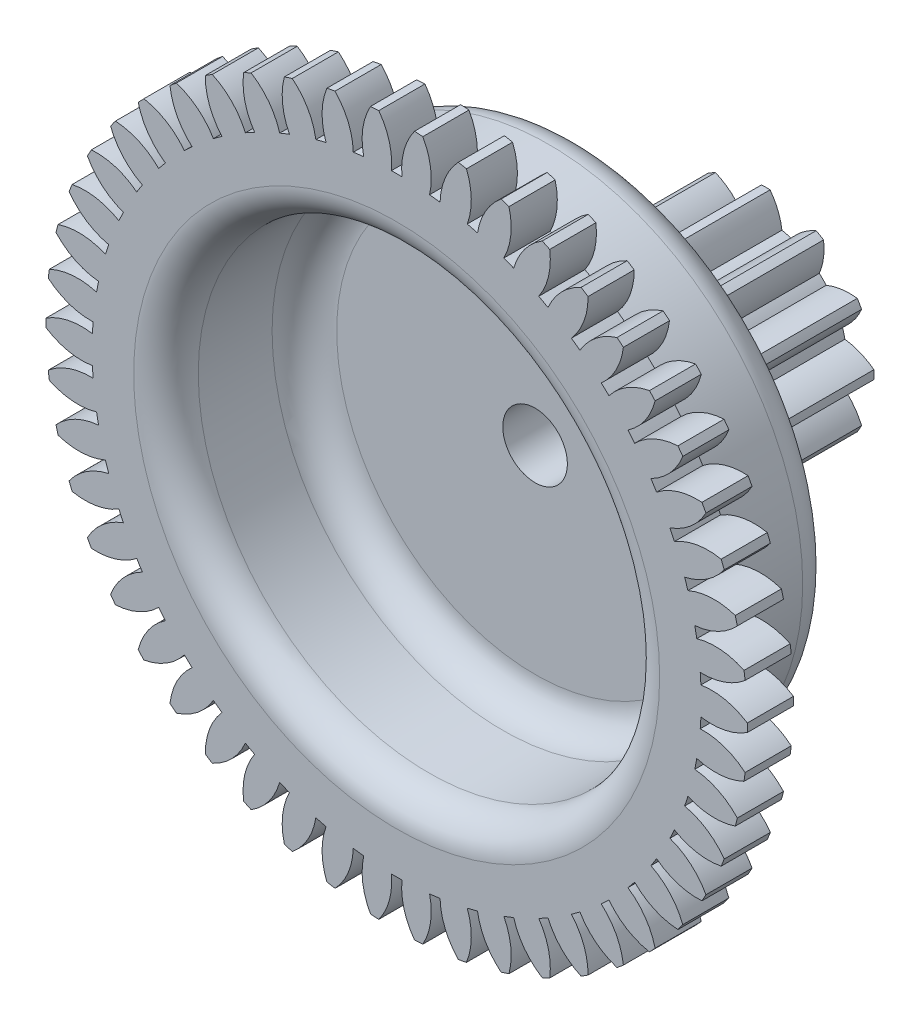
SolidWorks part; units mm, degrees
material "ABS PC"
ref_plane "Front Plane" through (0, 0, 0) normal (0, 0, 1) x (1, 0, 0)
ref_plane "Top Plane" through (0, 0, 0) normal (0, 1, 0) x (1, 0, 0)
ref_plane "Right Plane" through (0, 0, 0) normal (1, 0, 0) x (0, 0, -1)
sketch "Sketch1" plane through (0, 0, 0) normal (0, 0, 1) x (1, 0, 0)
  circle A0 centre (0, 0) radius 6.6
  dimension "D1" = 13.2
extrude "Extrude1" add sketch "Sketch1" along normal mid plane 1
sketch "Sketch2" plane through (0, 0, 0.5) normal (0, 0, 1) x (1, 0, 0)
  line L0 (-7.6, 0) -> (-6.6, 0) construction
  arc A2 (-6.5932, 0.3) -> (-6.5932, -0.3) centre (0, 0) ccw
  arc A3 (-7.5995, -0.09) -> (-6.5932, -0.3) centre (-6.8237, 1.1113) ccw
  arc A4 (-7.5995, 0.09) -> (-7.5995, -0.09) centre (0, 0) ccw
  arc A5 (-6.5932, 0.3) -> (-7.5995, 0.09) centre (-6.8235, -1.1124) ccw
  circle A12 centre (0, 0) radius 6.6 construction
  point P7 (0, 0)
  dimension "D1" = 1
  dimension "D2" = 1.4311
  dimension "D3" = 1.43
  dimension "D4" = 0.18
  dimension "D5" = 0.6
extrude "Extrude2" add sketch "Sketch2" against normal blind 1
pattern_circular "CirPattern1" count 50 over 360 about axis through (0, 0, 0.5) along (0, 0, -1) of "Extrude2"
sketch "Sketch3" plane through (0, 0, -0.5) normal (0, 0, -1) x (-1, 0, 0)
  circle A1 centre (0, 0) radius 5.5
  dimension "D2" = 11
extrude "Extrude4" add sketch "Sketch3" along normal blind 3
sketch "Sketch4" plane through (0, 0, -3.5) normal (0, 0, -1) x (-1, 0, 0)
  line L0 (0, 2.3452) -> (0, 0) construction
  arc A0 (-0.35, 1.7146) -> (0.35, 1.7146) centre (0, 0) ccw
  arc A1 (0.0929, 2.3433) -> (-0.0929, 2.3433) centre (0, 0) ccw
  arc A2 (-0.0929, 2.3433) -> (-0.35, 1.7146) centre (0.9732, 1.5404) ccw
  arc A6 (0.35, 1.7146) -> (0.0929, 2.3433) centre (-0.9732, 1.5404) ccw
  dimension "D1" = 3.5
  dimension "D2" = 1.3346
  dimension "D3" = 0.1857
  dimension "D4" = 0.7
  dimension "D5" = 2.3452
extrude "Extrude3" add sketch "Sketch4" along normal blind 4
pattern_circular "CirPattern2" count 12 over 360 about axis through (0, 0, -7.5) along (0, 0, 1) of "Extrude3"
sketch "Sketch5" plane through (0, 0, -7.5) normal (0, 0, -1) x (-1, 0, 0)
  circle A0 centre (0, 0) radius 0.7
  dimension "D1" = 1.4
extrude "Cut-Extrude2" cut sketch "Sketch5" against normal up to surface (8 mm away) up to face at (0, 0, 0.5)
sketch "Sketch6" plane through (0, 0, 0.5) normal (0, 0, 1) x (1, 0, 0)
  circle A0 centre (0, 0) radius 5
  circle A1 centre (0, 0) radius 0.7 construction
  circle A2 centre (0, 0) radius 0.7
  dimension "D1" = 10
extrude "Cut-Extrude4" cut sketch "Sketch6" against normal blind 3
fillet "Fillet1" radius 0.7 3 edges at (5, 0, 0.5) (-5.5, 0, -3.5) (5, 0, -2.5)
